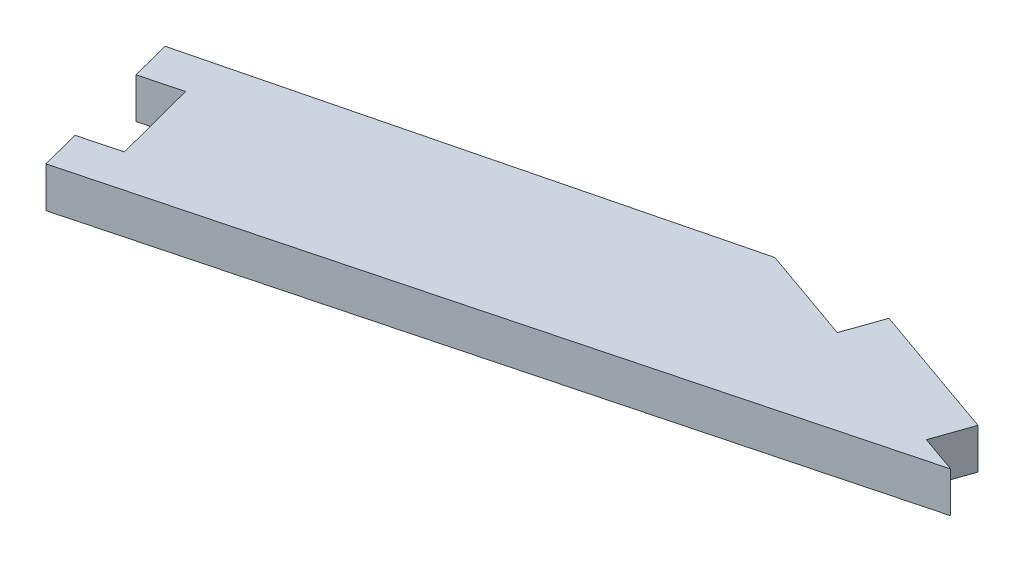
SolidWorks part; units mm, degrees
ref_plane "Front Plane" through (0, 0, 0) normal (0, 0, 1) x (1, 0, 0)
ref_plane "Top Plane" through (0, 0, 0) normal (0, 1, 0) x (1, 0, 0)
ref_plane "Right Plane" through (0, 0, 0) normal (1, 0, 0) x (0, 0, -1)
sketch "Sketch1" plane through (0, 0, 0) normal (0, 1, 0) x (1, 0, 0)
  line L0 (-450, 300) -> (-400, 300)
  line L1 (-400, 300) -> (-200, 250)
  line L2 (-200, 250) -> (200, 250) construction
  line L3 (200, 250) -> (600, 40) construction
  line L4 (600, 40) -> (1200, 40)
  line L5 (-450, -300) -> (-400, -300)
  line L6 (-400, -300) -> (-200, -250)
  line L7 (-200, -250) -> (200, -250) construction
  line L8 (200, -250) -> (600, -40) construction
  line L9 (600, -40) -> (1200, -40)
  line L10 (600, 40) -> (600, -40) construction
  line L11 (200, -250) -> (200, 250) construction
  line L12 (-200, 250) -> (-200, -250) construction
  line L13 (-400, -300) -> (-400, 300) construction
  line L14 (0, 0) -> (200, 0) construction
  line L15 (0, 250) -> (0, 0) construction
  line L16 (1200, 40) -> (1200, -40)
  line L17 (-450, 300) -> (-450, -300)
  line L18 (600, 0) -> (200, 0) construction
  line L19 (-450, 0) -> (-400, 0) construction
  line L20 (-400, 0) -> (-200, 0) construction
  line L21 (-200, 0) -> (0, 0) construction
  line L22 (-200, 250) -> (600, 40)
  line L23 (600, -40) -> (-200, -250)
  dimension "D1" = 600
  dimension "D2" = 200
  dimension "D3" = 50
  dimension "D4" = 400
  dimension "D5" = 500
  dimension "D6" = 80
  dimension "D7" = 600
  dimension "D8" = 400
extrude "Boss-Extrude1" add sketch "Sketch1" along normal blind 15
sketch "Sketch2" plane through (0, 0, 0) normal (0, 0, 1) x (1, 0, 0)
  line L0 (-450, 0) -> (-450, -40)
  line L1 (-450, -40) -> (-400, -40)
  line L2 (-400, -40) -> (-400, 0)
  line L3 (-400, 0) -> (-200, 0) construction
  line L4 (-400, 0) -> (-450, 0)
  line L5 (-440, -15) -> (-440, -40)
  line L6 (-410, -15) -> (-410, -40)
  line L7 (-425, 0) -> (-425, -15) construction
  circle A0 centre (-425, -15) radius 15
  dimension "D1" = 30
  dimension "D2" = 40
extrude "Boss-Extrude2" add sketch "Sketch2" along normal up to surface and the other way up to surface contours L4 L7 A0 L6 L1 L2 | L7 L4 L0 L1 L5 A0 up to face at (-425, 7.5, 300) other way up to face at (-425, 7.5, -300)
sketch "Sketch4" plane through (0, 0, 0) normal (0, 1, 0) x (1, 0, 0)
  line L0 (-450, 230) -> (-400, 230)
  line L1 (-450, 300) -> (-450, -300) construction
  line L2 (-400, 230) -> (-150, 167.5)
  line L3 (-150, 167.5) -> (-150, -167.5)
  line L4 (-150, -167.5) -> (-400, -230)
  line L5 (-400, -230) -> (-450, -230)
  line L6 (-400, 230) -> (-400, -230) construction
  line L7 (-200, 250) -> (-200, -250) construction
  line L9 (-200, 0) -> (-150, 0) construction
  line L10 (-400, -230) -> (-400, -300) construction
  line L11 (-400, -300) -> (-200, -250) construction
  line L12 (-450, 230) -> (-450, -230)
  line L14 (-200, 250) -> (-400, 300) construction
  line L15 (-100, 155) -> (-100, -155)
  line L16 (-100, -155) -> (520, 0)
  line L17 (520, 0) -> (-100, 155)
  line L18 (520, 0) -> (-100, 0) construction
  dimension "D1" = 460
  dimension "D2" = 300
  dimension "D3" = 50
extrude "Cut-Extrude2" cut sketch "Sketch4" against normal through all both and the other way through all
sketch "Sketch5" plane through (0, 0, 0) normal (1, 0, 0) x (0, 0, -1)
  line L0 (-300, 0) -> (-230, 0) construction
  line L1 (-285, 0) -> (-245, 0)
  line L2 (-285, 0) -> (-285, -40)
  line L3 (-285, -40) -> (-245, -40)
  line L4 (-245, 0) -> (-245, -40)
  line L5 (-300, -40) -> (-230, -40) construction
  line L6 (230, 0) -> (300, 0) construction
  line L7 (245, 0) -> (285, 0)
  line L8 (245, 0) -> (245, -40)
  line L9 (245, -40) -> (285, -40)
  line L10 (285, 0) -> (285, -40)
  line L11 (230, -40) -> (300, -40) construction
  line L12 (-300, 0) -> (-300, -40) construction
  line L13 (230, -40) -> (230, 0) construction
  line L14 (300, 0) -> (300, -40) construction
  dimension "D1" = 15
  dimension "D2" = 15
  dimension "D3" = 15
  dimension "D4" = 15
extrude "Cut-Extrude3" cut sketch "Sketch5" against normal through all
sketch "Sketch7" plane through (1200, 0, 0) normal (1, 0, 0) x (0, 0, -1)
  line L1 (-40, 15) -> (-87.5, 50)
  line L2 (-87.5, 50) -> (-87.5, 88.7)
  line L3 (-87.5, 88.7) -> (87.5, 88.7)
  line L4 (87.5, 88.7) -> (87.5, 50)
  line L5 (87.5, 50) -> (40, 15)
  line L7 (-40, 15) -> (40, 15)
  line L8 (-20, 50) -> (-20, 88.7)
  line L9 (87.5, 50) -> (-87.5, 50) construction
  line L10 (0, 88.7) -> (0, 50) construction
  line L11 (-20, 88.7) -> (20, 88.7)
  line L12 (0, 50) -> (0, 0) construction
  line L13 (20, 88.7) -> (20, 50)
  line L14 (-73, 88.7) -> (-63, 88.7)
  line L15 (-73, 88.7) -> (-73, 63.2)
  line L16 (-73, 63.2) -> (-63, 63.2)
  line L17 (-63, 88.7) -> (-63, 63.2)
  line L18 (48.5, 88.7) -> (58.5, 88.7)
  line L19 (48.5, 88.7) -> (48.5, 63.2)
  line L20 (48.5, 63.2) -> (58.5, 63.2)
  line L21 (58.5, 88.7) -> (58.5, 63.2)
  circle A0 centre (0, 50) radius 20
  dimension "D3" = 40
  dimension "D1" = 175
  dimension "D2" = 50
  dimension "D4" = 25.5
  dimension "D5" = 10
  dimension "D6" = 63
  dimension "D7" = 48.5
  dimension "D8" = 38.7
extrude "Boss-Extrude4" add sketch "Sketch7" against normal blind 75
sketch "Sketch8" plane through (0, 0, 0) normal (0, 0, 1) x (1, 0, 0)
  line L0 (1125, 88.7) -> (1200, 88.7) construction
  line L1 (1140, 88.7) -> (1185, 88.7)
  line L2 (1140, 88.7) -> (1140, 15)
  line L3 (1140, 15) -> (1185, 15)
  line L4 (1185, 88.7) -> (1185, 15)
  line L5 (1125, 15) -> (1200, 15) construction
  line L6 (1125, 50) -> (1125, 88.7) construction
  line L7 (1200, 50) -> (1200, 88.7) construction
  line L8 (1155, 88.7) -> (1170, 88.7) construction
  line L9 (1155, 88.7) -> (1170, 88.7)
  line L10 (1155, 88.7) -> (1155, 15)
  line L11 (1155, 15) -> (1170, 15)
  line L12 (1170, 88.7) -> (1170, 15)
  line L15 (1162.5, 50) -> (1162.5, 88.7) construction
  line L16 (1125, 50) -> (1200, 50) construction
  line L17 (1155, 88.7) -> (1170, 88.7) construction
  dimension "D1" = 15
  dimension "D2" = 15
  dimension "D3" = 15
extrude "Cut-Extrude4" cut sketch "Sketch8" against normal through all both and the other way through all contours L10 L1 L2 L3 | L1 L12 L3 L4
fillet "Fillet1" radius 5 53 edges at (1192.5, 50, 87.5) (1162.5, 50, 87.5) (1132.5, 50, 87.5) (1192.5, 50, -87.5) (1162.5, 50, -87.5) (1132.5, 50, -87.5) (1192.5, 88.7, -87.5) (1162.5, 88.7, -87.5) (1132.5, 88.7, -87.5) (1132.5, 88.7, -58.5) (1162.5, 88.7, -58.5) (1192.5, 88.7, -58.5) (1192.5, 88.7, -48.5) (1162.5, 88.7, -48.5) (1132.5, 88.7, -48.5) (1192.5, 88.7, -20) (1162.5, 88.7, -20) (1132.5, 88.7, -20) (1192.5, 88.7, 63) (1162.5, 88.7, 63) (1132.5, 88.7, 63) (1132.5, 88.7, 87.5) (1162.5, 88.7, 87.5) (1192.5, 88.7, 87.5) (1192.5, 88.7, 73) (1162.5, 88.7, 73) (1132.5, 88.7, 73) (1192.5, 88.7, 20) (1162.5, 88.7, 20) (1132.5, 88.7, 20) (600, 7.5, 40) (600, 7.5, -40) (520, 7.5, 0) (-440, -40, -292.5) (-440, -40, -237.5) (-400, -40, -292.5) (-400, -40, -237.5) (-450, -40, -237.5) (-410, -40, -237.5) (-450, -40, -292.5) (-410, -40, -292.5) (-150, 7.5, 167.5) (-100, 7.5, 155) (-150, 7.5, -167.5) (-100, 7.5, -155) (-450, -40, 237.5) (-410, -40, 237.5) (-440, -40, 237.5) (-400, -40, 237.5) (-450, -40, 292.5) (-440, -40, 292.5) (-400, -40, 292.5) (-410, -40, 292.5)
sketch "Sketch9" plane through (0, 0, 0) normal (0, 1, 0) x (1, 0, 0)
  line L35 (-450, -300) -> (-400, -300) construction
  line L36 (-425, -300) -> (-425, -285) construction
  line L37 (-450, 0) -> (0, 0) construction
  line L38 (-437.5, -300) -> (-412.5, -300)
  line L39 (-437.5, -300) -> (-437.5, -285)
  line L56 (1140, -40) -> (1140, -85.466) construction
  line L57 (1200, -40) -> (1185, -40)
  line L58 (1200, -40) -> (1200, -25)
  line L59 (1200, -25) -> (1185, -25)
  line L60 (1185, -40) -> (1185, -25)
  line L61 (1200, 40) -> (1185, 40)
  line L62 (1200, 40) -> (1200, 25)
  line L63 (1200, 25) -> (1185, 25)
  line L64 (1185, 40) -> (1185, 25)
  line L65 (1170, 40) -> (1155, 40)
  line L66 (1170, 40) -> (1170, 25)
  line L67 (1170, 25) -> (1155, 25)
  line L68 (1155, 40) -> (1155, 25)
  line L69 (1140, 40) -> (1125, 40)
  line L70 (1140, 40) -> (1140, 25)
  line L71 (1140, 25) -> (1125, 25)
  line L72 (1125, 40) -> (1125, 25)
  line L73 (1125, -40) -> (1140, -40)
  line L74 (1125, -40) -> (1125, -25)
  line L75 (1125, -25) -> (1140, -25)
  line L76 (1140, -40) -> (1140, -25)
  line L77 (1155, -40) -> (1170, -40)
  line L78 (1155, -40) -> (1155, -25)
  line L79 (1155, -25) -> (1170, -25)
  line L80 (1170, -40) -> (1170, -25)
  line L81 (600.6453, -40) -> (1200, -40) construction
  line L82 (1200, 40) -> (600.6453, 40) construction
  line L83 (1140, 40) -> (1125, 40) construction
  line L84 (1125, 85.466) -> (1125, 40) construction
  line L85 (1140, -25) -> (1155, -25) construction
  line L86 (1170, -25) -> (1185, -25) construction
  line L87 (1185, 25) -> (1170, 25) construction
  line L88 (1155, 25) -> (1140, 25) construction
  line L89 (-437.5, -285) -> (-412.5, -285)
  line L90 (-412.5, -300) -> (-412.5, -285)
  line L92 (-410, -230) -> (-440, -230) construction
  line L93 (-437.5, -230) -> (-412.5, -230)
  line L94 (-437.5, -230) -> (-437.5, -245)
  line L95 (-437.5, -245) -> (-412.5, -245)
  line L96 (-412.5, -230) -> (-412.5, -245)
  line L97 (-425, -245) -> (-400, -245) construction
  line L98 (-425, -285) -> (-425, -245) construction
  line L99 (-425, 285) -> (-425, 245) construction
  line L100 (-425, 300) -> (-425, 285) construction
  line L101 (-450, 300) -> (-400, 300) construction
  line L102 (-412.5, 230) -> (-412.5, 245)
  line L103 (-437.5, 245) -> (-412.5, 245)
  line L104 (-437.5, 230) -> (-437.5, 245)
  line L105 (-437.5, 230) -> (-412.5, 230)
  line L106 (-412.5, 300) -> (-412.5, 285)
  line L107 (-437.5, 285) -> (-412.5, 285)
  line L108 (-437.5, 300) -> (-437.5, 285)
  line L109 (-437.5, 300) -> (-412.5, 300)
  dimension "D1" = 15
  dimension "D2" = 25
  dimension "D3" = 15
extrude "Cut-Extrude5" cut sketch "Sketch9" against normal through all both and the other way through all
sketch "Sketch10" plane through (0, 0, 0) normal (0, 0, 1) x (1, 0, 0)
  line L1 (-450, 15) -> (1200, 15)
  line L2 (-450, 15) -> (-450, 0)
  line L3 (-450, 0) -> (1200, 0)
  line L4 (1200, 15) -> (1200, 0)
  line L5 (-450, 15) -> (-450, -35) construction
  line L6 (-486.0808, 110.0266) -> (1242.84, 110.0266)
  line L7 (-486.0808, 110.0266) -> (-486.0808, -68.8272)
  line L8 (-486.0808, -68.8272) -> (1242.84, -68.8272)
  line L9 (1242.84, 110.0266) -> (1242.84, -68.8272)
  dimension "D1" = 15
extrude "Cut-Extrude6" cut sketch "Sketch10" against normal through all both and the other way through all
sketch "Sketch11" plane through (0, 0, 0) normal (0, 1, 0) x (1, 0, 0)
  line L0 (-450, -315.625) -> (323.7848, -112.5065)
  line L1 (-200, -250) -> (599.3758, -40.1638) construction
  line L2 (-450, -315.625) -> (-450, -242.5)
  line L3 (-450, -230) -> (-450, -300) construction
  line L4 (-450, -242.5) -> (308.1542, -52.9615)
  line L5 (308.1542, -52.9615) -> (323.7848, -112.5065)
  line L6 (-400, -230) -> (-153.7873, -168.4468) construction
  line L7 (-450, -242.5) -> (-450, -230)
  line L8 (-450, -230) -> (-400, -230)
  line L9 (-150, -167.5) -> (-150, -182.5)
  line L10 (-150, -182.5) -> (-135, -182.5)
  line L11 (-135, -182.5) -> (-135, -163.75)
  line L12 (-100, -155) -> (-100, -182.5)
  line L13 (-100, -182.5) -> (-115, -182.5)
  line L14 (-115, -182.5) -> (-115, -158.75)
  line L15 (-100, 148.5961) -> (-100, -148.5961) construction
  line L16 (-150, -163.5961) -> (-150, 163.5961) construction
  line L17 (309.2763, -116.315) -> (305.4678, -101.8065)
  line L18 (-601.3695, -564.0724) -> (1251.3111, -564.0724)
  line L19 (-601.3695, -564.0724) -> (-601.3695, 511.8547)
  line L20 (-601.3695, 511.8547) -> (1251.3111, 511.8547)
  line L21 (1251.3111, -564.0724) -> (1251.3111, 511.8547)
  line L22 (305.4678, -101.8065) -> (319.9763, -97.998)
  line L23 (293.6011, -56.5997) -> (297.4095, -71.1082)
  line L24 (297.4095, -71.1082) -> (311.918, -67.2997)
  line L25 (305.4678, -101.8065) -> (297.4095, -71.1082) construction
  line L26 (323.7848, -112.5065) -> (600.6453, -40)
  line L27 (600.6453, -40) -> (500.5971, -4.8507)
  line L28 (500.5971, -4.8507) -> (308.1542, -52.9615)
  line L29 (574.7182, -46.79) -> (474.1575, -11.4606)
  line L30 (560.5662, -41.8181) -> (565.5382, -27.666)
  line L31 (509.7772, -23.9747) -> (514.7492, -9.8227)
  dimension "D1" = 800
  dimension "D2" = 15
  dimension "D3" = 15
  dimension "D4" = 15
  dimension "D5" = 15
  dimension "D6" = 15
  dimension "D7" = 15
  dimension "D8" = 15
extrude "Cut-Extrude7" cut sketch "Sketch11" along normal through all contours L18 L21 L20 L19 L28 L27 L26 L0 L2 L7 L8 L4 | L8 L7 L4 | L17 L25 L23 L4 L12 L13 L14 L11 L10 L9 L2 L0 | L10 L11 L4 L9 | L14 L13 L12 L4 | L30 L29 L26 L27 | L29 L31 L27 L28 | L25 L22 L5 L24
